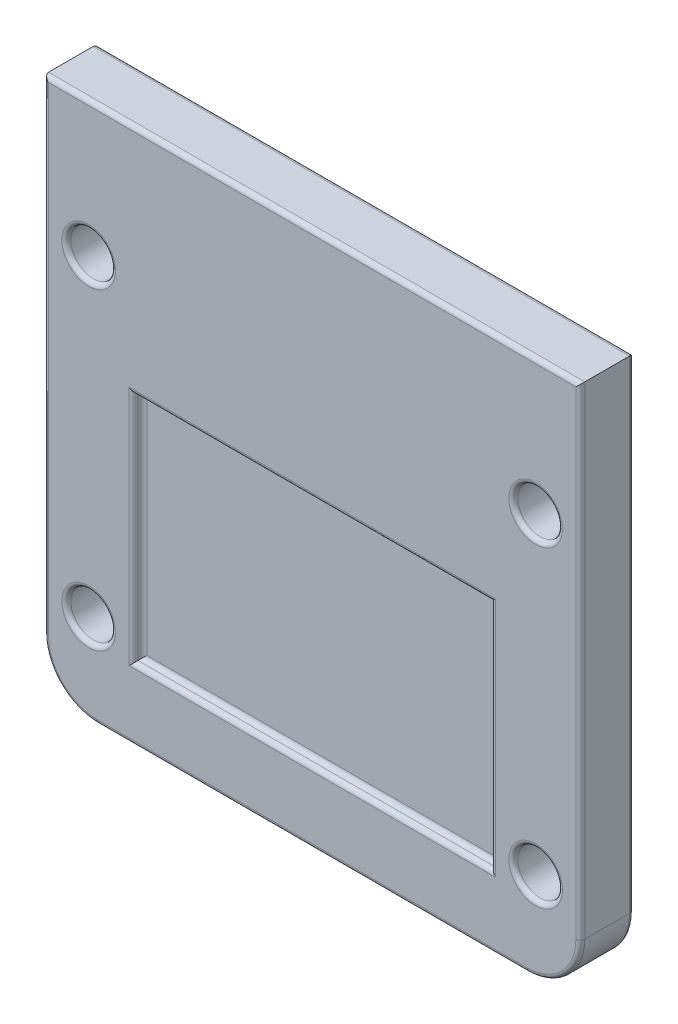
SolidWorks part; units mm, degrees
material "PET"
ref_plane "Front Plane" through (0, 0, 0) normal (0, 0, 1) x (1, 0, 0)
ref_plane "Top Plane" through (0, 0, 0) normal (0, 1, 0) x (1, 0, 0)
ref_plane "Right Plane" through (0, 0, 0) normal (1, 0, 0) x (0, 0, -1)
sketch "Sketch1" plane through (0, 0, 0) normal (0, 0, 1) x (1, 0, 0)
  line L1 (0, 0) -> (60, 0)
  line L2 (0, 0) -> (0, 60)
  line L3 (0, 60) -> (60, 60)
  line L4 (60, 0) -> (60, 60)
  dimension "D1" = 60
  dimension "D2" = 60
extrude "Boss-Extrude1" add sketch "Sketch1" along normal blind 6
sketch "Sketch2" plane through (0, 0, 6) normal (0, 0, 1) x (1, 0, 0)
  line L0 (0, 0) -> (60, 0) construction
  line L1 (10, 34) -> (50, 34)
  line L2 (10, 34) -> (10, 8)
  line L3 (10, 8) -> (50, 8)
  line L4 (50, 34) -> (50, 8)
  point P4 (30, 8)
  point P7 (30, 0)
  dimension "D1" = 26
  dimension "D2" = 40
  dimension "D3" = 8
hole_wizard "Ø5.0mm Dowel Hole1" positions "Sketch3" profile "Sketch4" hole size "Ø5.0" standard "ANSI Metric" end condition through all
sketch "Sketch3" plane through (0, 0, 6) normal (0, 0, 1) x (1, 0, 0)
  line L0 (0, 60) -> (0, 0) construction
  line L1 (0, 0) -> (60, 0) construction
  line L2 (60, 0) -> (60, 60) construction
  point P0 (5, 10)
  point P2 (55, 10)
  point P4 (55, 45)
  point P6 (5, 45)
  dimension "D1" = 5
  dimension "D2" = 10
  dimension "D3" = 35
  dimension "D4" = 5
sketch "Sketch4" plane through (5, 10, 6) normal (1, 0, 0) x (0, -1, 0)
  line L0 (0, 0) -> (0, 6)
  line L1 (0, 6) -> (2.5, 6)
  line L2 (2.5, 6) -> (2.5, 0)
  line L5 (2.5, 0) -> (0, 0)
  line L11 (0, -6.35) -> (0, 107.95) construction
  dimension "Thru Hole Dia." = 5
  dimension "Thru Hole Depth" = 6
fillet "Fillet1" radius 6 2 edges at (60, 0, 3) (0, 0, 3)
extrude "Cut-Extrude1" cut sketch "Sketch2" against normal blind 1
fillet "Fillet2" radius 0.5 28 edges at (30, 60, 0) (0, 33, 0) (1.7574, 1.7574, 0) (30, 0, 0) (58.2426, 1.7574, 0) (60, 33, 0) (7.5, 45, 0) (57.5, 45, 0) (57.5, 10, 0) (7.5, 10, 0) (1.7574, 1.7574, 6) (0, 33, 6) (30, 60, 6) (60, 33, 6) (58.2426, 1.7574, 6) (30, 0, 6) (7.5, 45, 6) (57.5, 45, 6) (57.5, 10, 6) (7.5, 10, 6) (50, 21, 6) (30, 34, 6) (10, 21, 6) (30, 8, 6) (30, 34, 5) (50, 21, 5) (30, 8, 5) (10, 21, 5)
